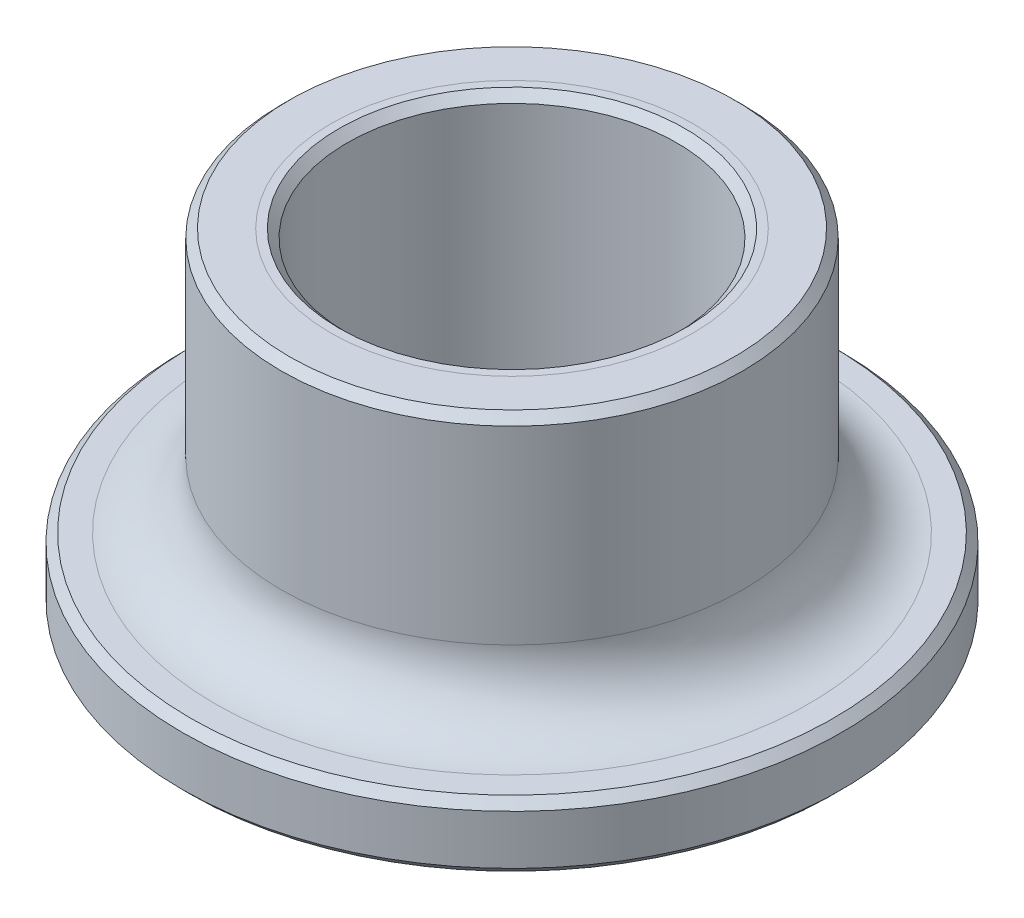
SolidWorks part; units mm, degrees
material "AISI 316 Annealed Stainless Steel Bar (SS)"
ref_plane "Front Plane" through (0, 0, 0) normal (0, 0, 1) x (1, 0, 0)
ref_plane "Top Plane" through (0, 0, 0) normal (0, 1, 0) x (1, 0, 0)
ref_plane "Right Plane" through (0, 0, 0) normal (1, 0, 0) x (0, 0, -1)
sketch "Sketch1" plane through (0, 0, 0) normal (0, 1, 0) x (1, 0, 0)
  circle A0 centre (0, 0) radius 10
  dimension "D1" = 20
extrude "Boss-Extrude1" add sketch "Sketch1" along normal blind 2
sketch "Sketch2" plane through (0, 2, 0) normal (0, 1, 0) x (1, 0, 0)
  circle A0 centre (0, 0) radius 7
  dimension "D1" = 14
extrude "Boss-Extrude2" add sketch "Sketch2" along normal blind 8
sketch "Sketch3" plane through (0, 10, 0) normal (0, 1, 0) x (1, 0, 0)
  circle A0 centre (0, 0) radius 5
  dimension "D1" = 10
extrude "Cut-Extrude1" cut sketch "Sketch3" against normal through all
sketch "Sketch4" plane through (0, 10, 0) normal (0, 1, 0) x (1, 0, 0)
  circle A2 centre (0, 0) radius 5.5
  circle A3 centre (0, 0) radius 5.5
  dimension "D1" = 0.5
split line "Split Line1"
chamfer "Chamfer1" distance 0.25 angle 45 5 edges at (0, 2, 10) (0, 0, 5) (0, 10, 5) (0, 0, 10) (0, 10, 7)
fillet "Fillet1" radius 2 1 edges at (0, 2, 7)
